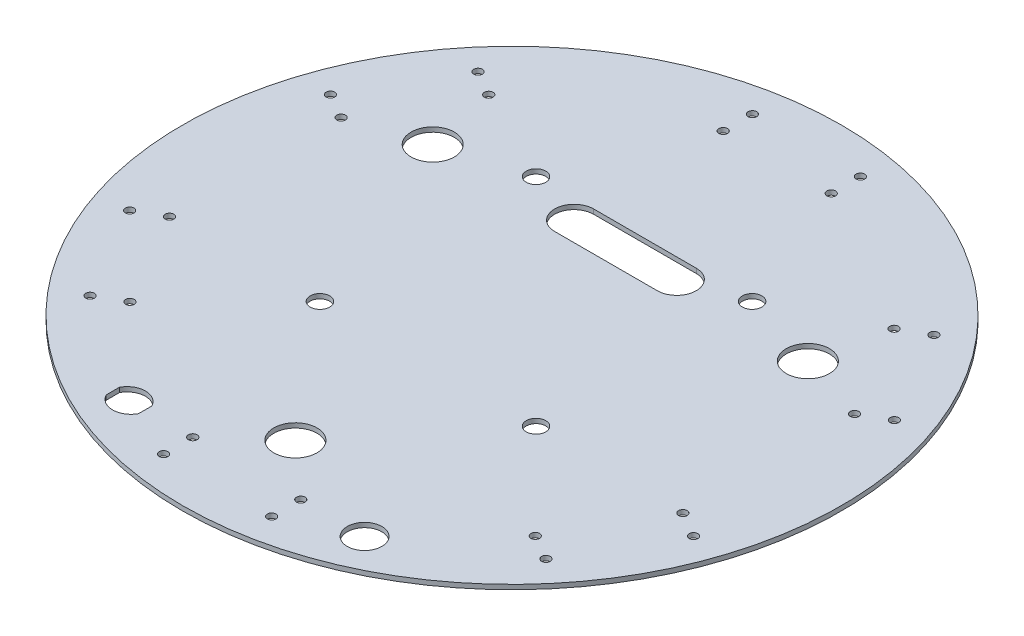
SolidWorks part; units mm, degrees
ref_plane "Front Plane" through (0, 0, 0) normal (0, 0, 1) x (1, 0, 0)
ref_plane "Top Plane" through (0, 0, 0) normal (0, 1, 0) x (1, 0, 0)
ref_plane "Right Plane" through (0, 0, 0) normal (1, 0, 0) x (0, 0, -1)
sketch "Sketch1" plane through (0, 0, 0) normal (0, 1, 0) x (1, 0, 0)
  line L0 (0, -152.5) -> (0, 152.5) construction
  line L1 (152.5, 0) -> (-152.5, 0) construction
  line L2 (-25, -136.225) -> (-25, -124.725) construction
  line L3 (-23.75, 52.5) -> (23.75, 52.5) construction
  line L4 (-23.75, 61.525) -> (23.75, 61.525)
  line L5 (-23.75, 43.475) -> (23.75, 43.475)
  line L6 (25, -122.725) -> (54.5, -122.725) construction
  line L7 (-62, -125.8) -> (-62, -119.65)
  line L8 (-47, -125.8) -> (-47, -119.65)
  line L9 (-47, -122.725) -> (-25, -122.725) construction
  circle A0 centre (0, 0) radius 152.5
  circle A1 centre (-25, -136.225) radius 2
  circle A2 centre (-25, -122.725) radius 2
  circle A3 centre (25, -136.225) radius 2
  circle A4 centre (25, -122.725) radius 2
  circle A5 centre (-118.783, -39.7119) radius 2
  circle A6 centre (-130.4743, -46.4619) radius 2
  circle A7 centre (-93.783, -83.0131) radius 2
  circle A8 centre (-105.4743, -89.7631) radius 2
  circle A9 centre (-93.783, 83.0131) radius 2
  circle A10 centre (-105.4743, 89.7631) radius 2
  circle A11 centre (-118.783, 39.7119) radius 2
  circle A12 centre (-130.4743, 46.4619) radius 2
  circle A13 centre (25, 122.725) radius 2
  circle A14 centre (25, 136.225) radius 2
  circle A15 centre (-25, 122.725) radius 2
  circle A16 centre (-25, 136.225) radius 2
  circle A17 centre (118.783, 39.7119) radius 2
  circle A18 centre (130.4743, 46.4619) radius 2
  circle A19 centre (93.783, 83.0131) radius 2
  circle A20 centre (105.4743, 89.7631) radius 2
  circle A21 centre (93.783, -83.0131) radius 2
  circle A22 centre (105.4743, -89.7631) radius 2
  circle A23 centre (118.783, -39.7119) radius 2
  circle A24 centre (130.4743, -46.4619) radius 2
  arc A25 (-23.75, 61.525) -> (-23.75, 43.475) centre (-23.75, 52.5) ccw
  arc A26 (23.75, 43.475) -> (23.75, 61.525) centre (23.75, 52.5) ccw
  circle A27 centre (0, -100.225) radius 10
  circle A28 centre (-86.7974, 50.1125) radius 10
  circle A29 centre (86.7974, 50.1125) radius 10
  arc A32 (-62, -119.65) -> (-47, -119.65) centre (-54.5, -123.6061) cw
  arc A33 (-62, -125.8) -> (-47, -125.8) centre (-54.5, -121.8439) ccw
  circle A34 centre (54.5, -122.725) radius 8
  circle A35 centre (-50, 61.1161) radius 4.5
  circle A36 centre (-50, -38.8839) radius 4.5
  circle A37 centre (50, -38.8839) radius 4.5
  circle A38 centre (50, 61.1161) radius 4.5
  point P18 (0, 52.5)
  point P59 (0, 0)
  point P72 (0, 0)
  point P73 (-54.5, -122.725)
  dimension "D1" = 305
  dimension "D2" = 138.5
  dimension "D4" = 4
  dimension "D10" = 20
  dimension "D14" = 16
  dimension "D17" = 9
  dimension "D18" = 100
  dimension "D20" = 50
  dimension "D3" = 25
  dimension "D5" = 13.5
  dimension "D7" = 18.05
  dimension "D8" = 47.5
  dimension "D9" = 100
  dimension "D11" = 22.5
  dimension "D13" = 15
  dimension "D15" = 22
  dimension "D16" = 29.5
  dimension "D19" = 63.34
  dimension "D6" = 6
  dimension "D12" = 3
extrude "Boss-Extrude1" add sketch "Sketch1" along normal blind 2.15
ref_axis "GroundMateAxis" through (0, 2.15, 13.3488) along (0, 0, -1)
